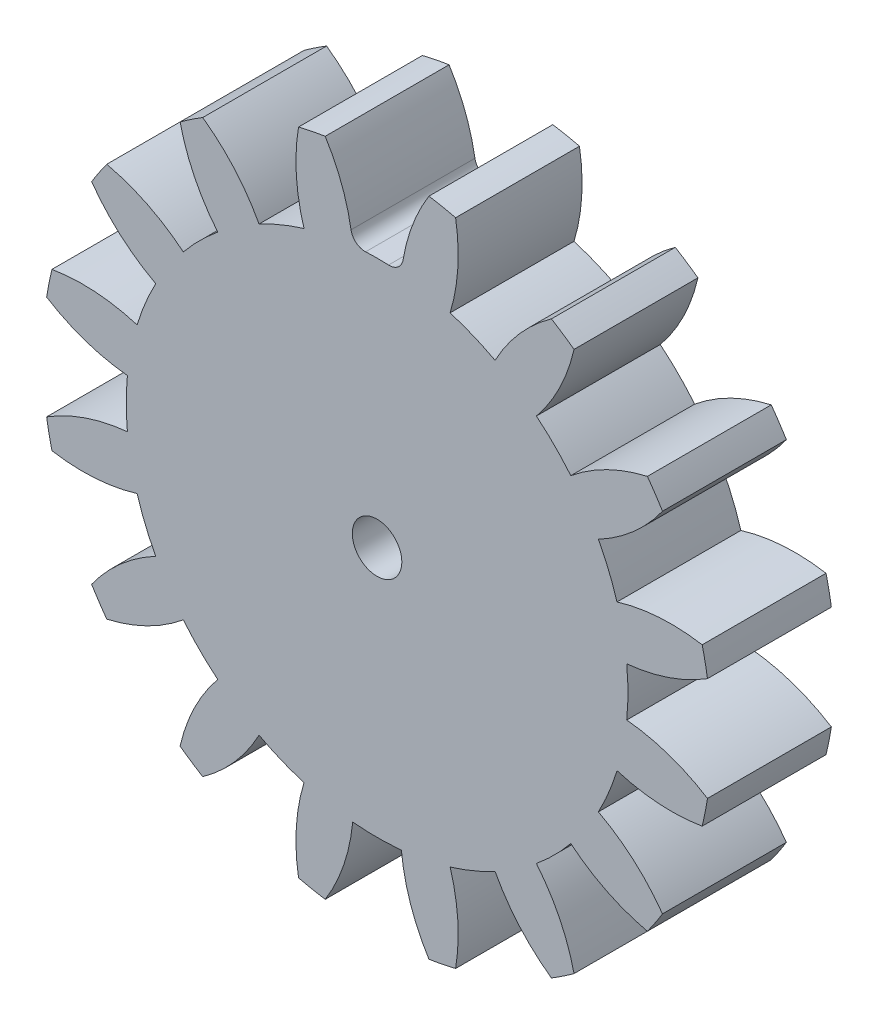
SolidWorks part; units mm, degrees
ref_plane "Front Plane" through (0, 0, 0) normal (0, 0, 1) x (1, 0, 0)
ref_plane "Top Plane" through (0, 0, 0) normal (0, 1, 0) x (1, 0, 0)
ref_plane "Right Plane" through (0, 0, 0) normal (1, 0, 0) x (0, 0, -1)
sketch "Sketch1" plane through (0, 0, 0) normal (0, 0, 1) x (1, 0, 0)
  circle A0 centre (0, 0) radius 13.5
  circle A1 centre (0, 0) radius 1
  dimension "D1" = 2
  dimension "D2" = 27
extrude "Boss-Extrude1" add sketch "Sketch1" along normal mid plane 5
sketch "Sketch2" plane through (0, 0, 0) normal (0, 0, 1) x (1, 0, 0)
  line L0 (0, 0) -> (0, 13.5) construction
  line L1 (0, 0) -> (-0.9822, 10.0772) construction
  line L2 (0, 8.0719) -> (-4.4336, 20.253) construction
  arc A0 (1.3999, 11.9181) -> (-1.3999, 11.9181) centre (0, 0) ccw construction
  arc A1 (0.9822, 10.0772) -> (-0.9822, 10.0772) centre (0, 0) ccw
  circle A2 centre (0, 0) radius 13.5 construction
  arc A3 (2.0928, 13.3368) -> (-2.0928, 13.3368) centre (0, 0) ccw
  arc A4 (-0.9822, 10.0772) -> (-2.0928, 13.3368) centre (-8.4601, 9.3484) ccw
  arc A5 (0.9822, 10.0772) -> (2.0928, 13.3368) centre (8.4601, 9.3484) cw
  dimension "D1" = 24
  dimension "D2" = 3.375
  dimension "D3" = 20
  dimension "D4" = 2.8062
extrude "Cut-Extrude1" cut sketch "Sketch2" against normal through all both and the other way through all
fillet "Fillet1" radius 0.57 2 edges at (0.9822, 10.0772, 0) (-0.9822, 10.0772, 0)
pattern_circular "CirPattern3" count 16 over 360 about axis through (0, 0, 2.5) along (0, 0, -1) of "Cut-Extrude1"
equation "\"Module\" = 1.5"
equation "\"Pressure Angle\"= 20"
equation "\"Bore\"= 2"
equation "\"NumTeeth\"= 16"
equation "\"D1@Sketch1\"=\"Bore\""
equation "\"D2@Sketch1\"=(\"NumTeeth\"+2)*\"Module\""
equation "\"D1@Sketch2\"=\"NumTeeth\"*\"Module\""
equation "\"ToothDepth\"= IIF ( \"Module\" < 1.25 , 2.4 * \"Module\" , 2.25 * \"Module\" )"
equation "\"D2@Sketch2\"=\"ToothDepth\""
equation "\"D3@Sketch2\"=\"Pressure Angle\""
equation "\"D4@Sketch2\"=((\"Module\"*PI)/2)+0.3*\"Module\""
equation "\"D1@Fillet1\"=\"Module\"*0.38"
equation "\"D1@CirPattern3\"=\"NumTeeth\""
